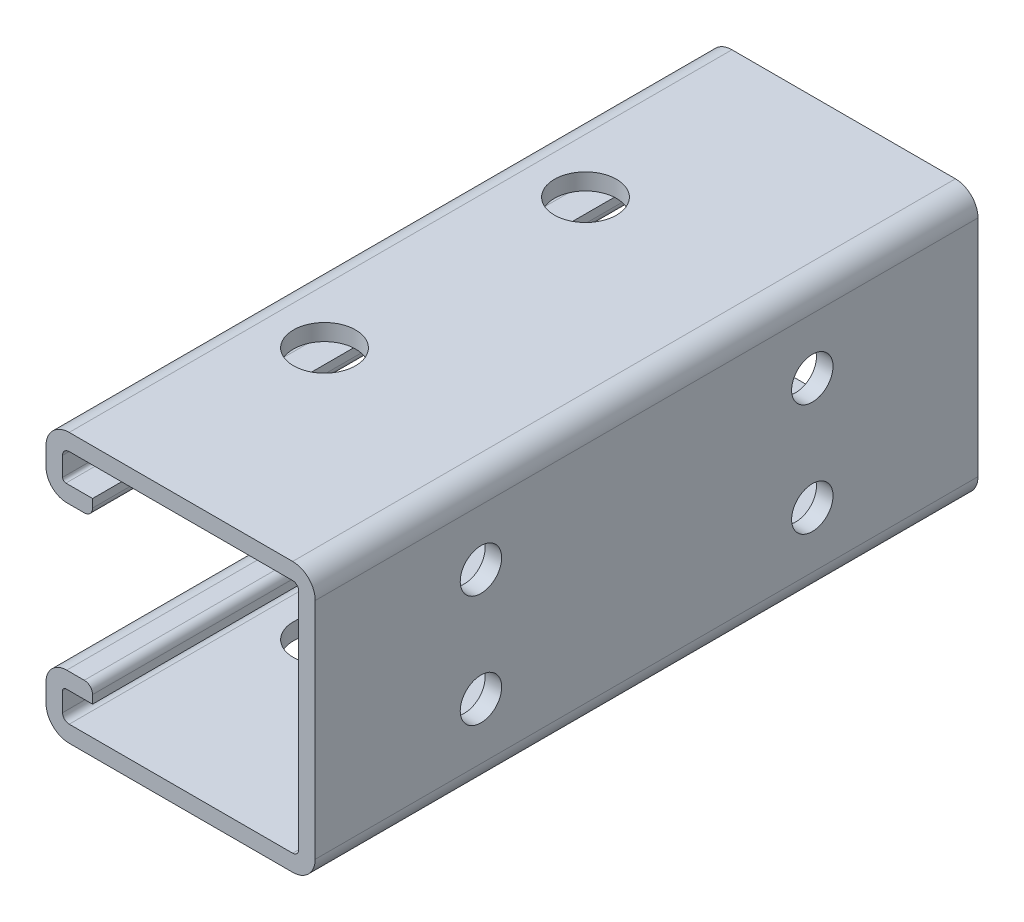
SolidWorks part; units mm, degrees
ref_plane "Front Plane" through (0, 0, 0) normal (0, 0, 1) x (1, 0, 0)
ref_plane "Top Plane" through (0, 0, 0) normal (0, 1, 0) x (1, 0, 0)
ref_plane "Right Plane" through (0, 0, 0) normal (1, 0, 0) x (0, 0, -1)
sketch "Sketch1" plane through (0, 0, 0) normal (0, 0, 1) x (1, 0, 0)
  line L0 (20.6375, 0) -> (-20.6375, 0) construction
  line L3 (-20.6375, 20.6375) -> (20.6375, 20.6375) construction
  line L4 (-20.6375, 20.6375) -> (-20.6375, -20.6375) construction
  line L5 (-20.6375, -20.6375) -> (20.6375, -20.6375) construction
  line L6 (20.6375, 20.6375) -> (20.6375, -20.6375) construction
  line L7 (-17.0815, 20.6375) -> (17.1768, 20.6375)
  line L8 (20.6375, 17.1767) -> (20.6375, -17.1767)
  line L9 (18.0975, -17.1767) -> (18.0975, 17.1767)
  line L10 (17.1768, 18.0975) -> (-17.0815, 18.0975)
  line L11 (-20.6375, 17.0815) -> (-20.6375, 14.2875)
  line L12 (-17.4625, 11.1125) -> (-14.7701, 11.1125)
  line L14 (-13.5001, 13.6525) -> (-17.5895, 13.6525)
  line L15 (-18.0975, 14.1605) -> (-18.0975, 17.0815)
  line L16 (-18.0975, -14.1605) -> (-18.0975, -17.0815)
  line L17 (-13.5001, -13.6525) -> (-17.5895, -13.6525)
  line L18 (-17.4625, -11.1125) -> (-14.7701, -11.1125)
  line L19 (-20.6375, -17.0815) -> (-20.6375, -14.2875)
  line L20 (17.1768, -18.0975) -> (-17.0815, -18.0975)
  line L21 (-17.0815, -20.6375) -> (17.1768, -20.6375)
  line L22 (18.0975, -20.6375) -> (18.0975, 20.6375) construction
  line L23 (-13.5001, 13.6525) -> (-13.5001, 12.3825)
  line L24 (-13.5001, 12.3825) -> (-13.5001, 11.1125) construction
  line L25 (-13.5001, -13.6525) -> (-13.5001, -12.3825)
  arc A1 (20.6375, 17.1767) -> (17.1768, 20.6375) centre (17.1768, 17.1767) ccw
  arc A2 (18.0975, 17.1767) -> (17.1768, 18.0975) centre (17.1768, 17.1767) ccw
  arc A4 (-17.0815, 20.6375) -> (-20.6375, 17.0815) centre (-17.0815, 17.0815) ccw
  arc A5 (-20.6375, 14.2875) -> (-17.4625, 11.1125) centre (-17.4625, 14.2875) ccw
  arc A6 (-13.5001, 12.3825) -> (-14.7701, 11.1125) centre (-14.7701, 12.3825) cw
  arc A7 (-17.5895, 13.6525) -> (-18.0975, 14.1605) centre (-17.5895, 14.1605) cw
  arc A8 (-18.0975, 17.0815) -> (-17.0815, 18.0975) centre (-17.0815, 17.0815) cw
  arc A9 (-18.0975, -17.0815) -> (-17.0815, -18.0975) centre (-17.0815, -17.0815) ccw
  arc A10 (-17.5895, -13.6525) -> (-18.0975, -14.1605) centre (-17.5895, -14.1605) ccw
  arc A11 (-13.5001, -12.3825) -> (-14.7701, -11.1125) centre (-14.7701, -12.3825) ccw
  arc A12 (-20.6375, -14.2875) -> (-17.4625, -11.1125) centre (-17.4625, -14.2875) cw
  arc A13 (-17.0815, -20.6375) -> (-20.6375, -17.0815) centre (-17.0815, -17.0815) cw
  arc A14 (18.0975, -17.1767) -> (17.1768, -18.0975) centre (17.1768, -17.1767) cw
  arc A15 (20.6375, -17.1767) -> (17.1768, -20.6375) centre (17.1768, -17.1767) cw
  point P24 (20.6375, 20.6375)
  point P65 (18.0975, 0)
  dimension "D1" = 3.4608
  dimension "D2" = 3.556
  dimension "D3" = 3.175
  dimension "D5" = 0.508
  dimension "Channel Height" = 41.275
  dimension "Channel Width" = 41.275
  dimension "Thickness" = 2.54
  dimension "Inside Channel Width" = 22.225
  dimension "D4" = 7.1374
  dimension "D6" = 2.54
  dimension "D7" = 3.5814
sketch "Sketch3" plane through (0, 0, 0) normal (1, 0, 0) x (0, 0, -1)
  line L0 (-152.4, 0) -> (152.4, 0) construction
  point P2 (-69.85, 0)
  point P3 (69.85, 0)
  dimension "D1" = 82.55
  dimension "D2" = 82.55
  dimension "Length" = 304.8
sketch "Sketch4" plane through (0, 0, 0) normal (0, 0, 1) x (1, 0, 0)
  line L16 (-17.0815, -20.6375) -> (17.1768, -20.6375)
  line L17 (-20.6375, -14.2875) -> (-20.6375, -17.0815)
  line L18 (-14.7701, -11.1125) -> (-17.4625, -11.1125)
  line L19 (-13.5001, -13.6525) -> (-13.5001, -12.3825)
  line L20 (-17.5895, -13.6525) -> (-13.5001, -13.6525)
  line L21 (-18.0975, -17.0815) -> (-18.0975, -14.1605)
  line L22 (17.1768, -18.0975) -> (-17.0815, -18.0975)
  line L23 (18.0975, 17.1767) -> (18.0975, -17.1767)
  line L24 (-17.0815, 18.0975) -> (17.1768, 18.0975)
  line L25 (-18.0975, 14.1605) -> (-18.0975, 17.0815)
  line L26 (-13.5001, 13.6525) -> (-17.5895, 13.6525)
  line L27 (-13.5001, 12.3825) -> (-13.5001, 13.6525)
  line L28 (-17.4625, 11.1125) -> (-14.7701, 11.1125)
  line L29 (-20.6375, 17.0815) -> (-20.6375, 14.2875)
  line L30 (17.1768, 20.6375) -> (-17.0815, 20.6375)
  line L31 (20.6375, -17.1767) -> (20.6375, 17.1767)
  line L32 (-17.0815, -20.6375) -> (17.1768, -20.6375)
  line L33 (-20.6375, -14.2875) -> (-20.6375, -17.0815)
  line L34 (-14.7701, -11.1125) -> (-17.4625, -11.1125)
  line L35 (-13.5001, -13.6525) -> (-13.5001, -12.3825)
  line L36 (-17.5895, -13.6525) -> (-13.5001, -13.6525)
  line L37 (-18.0975, -17.0815) -> (-18.0975, -14.1605)
  line L38 (17.1768, -18.0975) -> (-17.0815, -18.0975)
  line L39 (18.0975, 17.1767) -> (18.0975, -17.1767)
  line L40 (-17.0815, 18.0975) -> (17.1768, 18.0975)
  line L41 (-18.0975, 14.1605) -> (-18.0975, 17.0815)
  line L42 (-13.5001, 13.6525) -> (-17.5895, 13.6525)
  line L43 (-13.5001, 12.3825) -> (-13.5001, 13.6525)
  line L44 (-17.4625, 11.1125) -> (-14.7701, 11.1125)
  line L45 (-20.6375, 17.0815) -> (-20.6375, 14.2875)
  line L46 (17.1768, 20.6375) -> (-17.0815, 20.6375)
  line L47 (20.6375, -17.1767) -> (20.6375, 17.1767)
  arc A14 (-20.6375, -17.0815) -> (-17.0815, -20.6375) centre (-17.0815, -17.0815) ccw
  arc A15 (-17.4625, -11.1125) -> (-20.6375, -14.2875) centre (-17.4625, -14.2875) ccw
  arc A16 (-13.5001, -12.3825) -> (-14.7701, -11.1125) centre (-14.7701, -12.3825) ccw
  arc A17 (-17.5895, -13.6525) -> (-18.0975, -14.1605) centre (-17.5895, -14.1605) ccw
  arc A18 (-18.0975, -17.0815) -> (-17.0815, -18.0975) centre (-17.0815, -17.0815) ccw
  arc A19 (17.1768, -18.0975) -> (18.0975, -17.1767) centre (17.1768, -17.1767) ccw
  arc A20 (18.0975, 17.1767) -> (17.1768, 18.0975) centre (17.1768, 17.1767) ccw
  arc A21 (-17.0815, 18.0975) -> (-18.0975, 17.0815) centre (-17.0815, 17.0815) ccw
  arc A22 (-18.0975, 14.1605) -> (-17.5895, 13.6525) centre (-17.5895, 14.1605) ccw
  arc A23 (-14.7701, 11.1125) -> (-13.5001, 12.3825) centre (-14.7701, 12.3825) ccw
  arc A24 (-20.6375, 14.2875) -> (-17.4625, 11.1125) centre (-17.4625, 14.2875) ccw
  arc A25 (-17.0815, 20.6375) -> (-20.6375, 17.0815) centre (-17.0815, 17.0815) ccw
  arc A26 (20.6375, 17.1767) -> (17.1768, 20.6375) centre (17.1768, 17.1767) ccw
  arc A27 (17.1768, -20.6375) -> (20.6375, -17.1767) centre (17.1768, -17.1767) ccw
  arc A28 (-20.6375, -17.0815) -> (-17.0815, -20.6375) centre (-17.0815, -17.0815) ccw
  arc A29 (-17.4625, -11.1125) -> (-20.6375, -14.2875) centre (-17.4625, -14.2875) ccw
  arc A30 (-13.5001, -12.3825) -> (-14.7701, -11.1125) centre (-14.7701, -12.3825) ccw
  arc A31 (-17.5895, -13.6525) -> (-18.0975, -14.1605) centre (-17.5895, -14.1605) ccw
  arc A32 (-18.0975, -17.0815) -> (-17.0815, -18.0975) centre (-17.0815, -17.0815) ccw
  arc A33 (17.1768, -18.0975) -> (18.0975, -17.1767) centre (17.1768, -17.1767) ccw
  arc A34 (18.0975, 17.1767) -> (17.1768, 18.0975) centre (17.1768, 17.1767) ccw
  arc A35 (-17.0815, 18.0975) -> (-18.0975, 17.0815) centre (-17.0815, 17.0815) ccw
  arc A36 (-18.0975, 14.1605) -> (-17.5895, 13.6525) centre (-17.5895, 14.1605) ccw
  arc A37 (-14.7701, 11.1125) -> (-13.5001, 12.3825) centre (-14.7701, 12.3825) ccw
  arc A38 (-20.6375, 14.2875) -> (-17.4625, 11.1125) centre (-17.4625, 14.2875) ccw
  arc A39 (-17.0815, 20.6375) -> (-20.6375, 17.0815) centre (-17.0815, 17.0815) ccw
  arc A40 (20.6375, 17.1767) -> (17.1768, 20.6375) centre (17.1768, 17.1767) ccw
  arc A41 (17.1768, -20.6375) -> (20.6375, -17.1767) centre (17.1768, -17.1767) ccw
  dimension "D1" = 0
extrude "Boss-Extrude1" add sketch "Sketch4" along normal blind 50.8 and the other way blind 50.8
sketch "Sketch7" plane through (0, 20.6375, 0) normal (0, 1, 0) x (1, 0, 0)
  line L0 (17.1768, 0) -> (-17.0815, 0) construction
  line L1 (17.1768, 50.8) -> (17.1768, -50.8) construction
  line L2 (-17.0815, 50.8) -> (-17.0815, -50.8) construction
  circle A0 centre (-8.7376, -20) radius 4.7625
  circle A1 centre (-8.7376, 20) radius 4.7625
  point P6 (-8.7376, -20)
  dimension "D3" = 9.525
  dimension "D1" = 20
  dimension "D2" = 8.3439
extrude "Cut-Extrude1" cut sketch "Sketch7" against normal blind 45.72
sketch "Sketch8" plane through (20.6375, 0, 0) normal (1, 0, 0) x (0, 0, -1)
  line L0 (0, 0) -> (0, -17.1767) construction
  line L1 (-50.8, -17.1767) -> (50.8, -17.1767) construction
  line L2 (-50.8, -17.1767) -> (-50.8, 17.1767) construction
  line L3 (-50.8, 17.1767) -> (50.8, 17.1767) construction
  line L4 (50.8, -17.1767) -> (50.8, 17.1767) construction
  line L5 (-50.8, -17.1767) -> (50.8, 17.1767) construction
  line L6 (-50.8, 17.1767) -> (50.8, -17.1767) construction
  line L7 (0, 0) -> (50.8, 0) construction
  line L8 (25.4, 0) -> (25.4, -17.1767) construction
  line L9 (0, -8.5884) -> (50.8, -8.5884) construction
  circle A0 centre (25.4, -8.5884) radius 3.175
  circle A1 centre (25.4, 8.5884) radius 3.175
  circle A2 centre (-25.4, -8.5884) radius 3.175
  circle A3 centre (-25.4, 8.5884) radius 3.175
  point P0 (0, 0)
  dimension "D1" = 6.35
  dimension "D2" = 34.3535
extrude "Cut-Extrude2" cut sketch "Sketch8" against normal up to surface (2.54 mm away) up to face at (18.0975, 0, 0)
equation "\"D1@Sketch3\" = \"Channel Height@Sketch1\" * 2"
equation "\"D2@Sketch3\"=\"D1@Sketch3\""
equation "\"D6@Sketch1\"=\"Thickness@Sketch1\""
